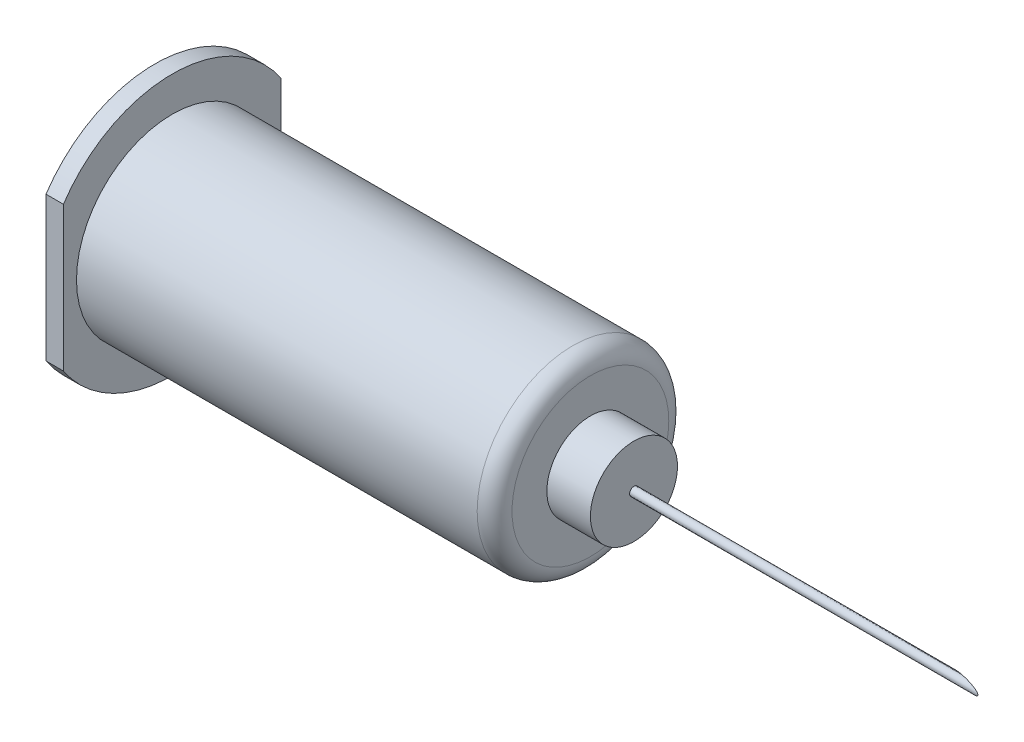
SolidWorks part; units mm, degrees
ref_plane "Alzado" through (0, 0, 0) normal (0, 0, 1) x (1, 0, 0)
ref_plane "Planta" through (0, 0, 0) normal (0, 1, 0) x (1, 0, 0)
ref_plane "Vista lateral" through (0, 0, 0) normal (1, 0, 0) x (0, 0, -1)
sketch "Croquis2" plane through (0, 0, 0) normal (1, 0, 0) x (0, 0, -1)
  circle A0 centre (0, 0) radius 11
  dimension "D1" = 22
extrude "Saliente-Extruir1" add sketch "Croquis2" along normal blind 50
fillet "Redondeo1" radius 2 1 edges at (50, 0, -11)
sketch "Croquis4" plane through (50, 0, 0) normal (1, 0, 0) x (0, 0, -1)
  circle A0 centre (0, 0) radius 5
  dimension "D1" = 10
extrude "Saliente-Extruir2" add sketch "Croquis4" along normal blind 5
sketch "Croquis5" plane through (55, 0, 0) normal (1, 0, 0) x (0, 0, -1)
  circle A0 centre (0, 0) radius 0.5
  dimension "D1" = 1
extrude "Saliente-Extruir3" add sketch "Croquis5" along normal blind 40
shell "Vaciado1" thickness 1 removed face at (0, 0, -11)
sketch "Croquis6" plane through (54, 0, 0) normal (-1, 0, 0) x (0, 0, 1)
  circle A0 centre (0, 0) radius 0.5
  dimension "D1" = 1
extrude "Saliente-Extruir4" add sketch "Croquis6" along normal blind 25
sketch "Croquis7" plane through (0, 0, 0) normal (0, 1, 0) x (1, 0, 0)
  line L0 (95, -0.5) -> (91.0226, 0.5)
  line L1 (95, 0.5) -> (55, 0.5) construction
  line L2 (91.0226, 0.5) -> (95, 0.5)
  line L3 (95, 0.5) -> (95, -0.5)
  line L4 (95, 0.5) -> (55, 0.5) construction
extrude "Cortar-Extruir2" cut sketch "Croquis7" against normal mid plane 25
sketch "Croquis8" plane through (29, 0, 0) normal (-1, 0, 0) x (0, 0, 1)
  circle A0 centre (0, 0) radius 0.4
  dimension "D1" = 0.8
extrude "Cortar-Extruir3" cut sketch "Croquis8" against normal blind 72
sketch "Croquis9" plane through (0, 0, 0) normal (1, 0, 0) x (0, 0, -1)
  line L2 (12.5, -8.2916) -> (12.5, 8.2916)
  line L4 (-12.5, -8.2916) -> (-12.5, 8.2916)
  line L5 (7.0711, -7.0711) -> (-7.0711, 7.0711) construction
  line L6 (7.0711, 7.0711) -> (-7.0711, -7.0711) construction
  circle A0 centre (0, 0) radius 10
  arc A1 (-12.5, -8.2916) -> (12.5, -8.2916) centre (0, 0) ccw
  arc A2 (12.5, 8.2916) -> (-12.5, 8.2916) centre (0, 0) ccw
  dimension "D1" = 30
  dimension "D2" = 20
extrude "Saliente-Extruir5" add sketch "Croquis9" along normal blind 2 separate body
